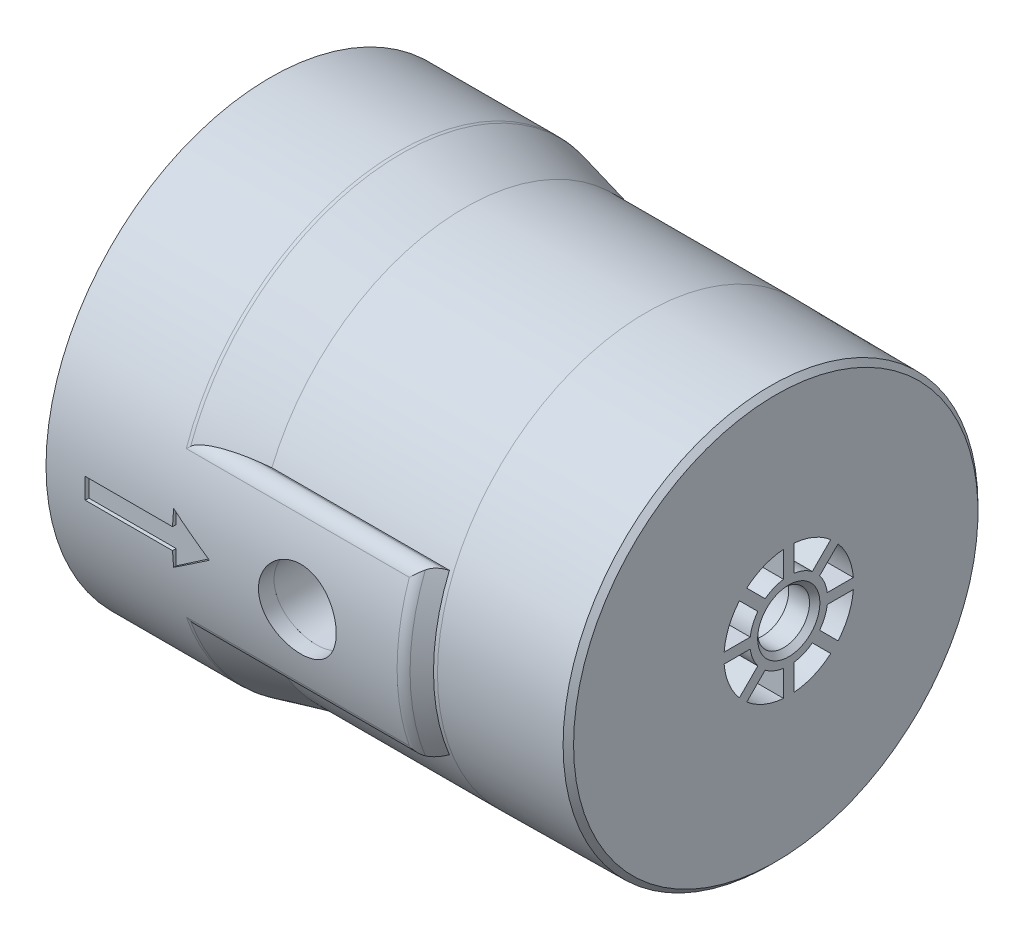
SolidWorks part; units mm, degrees
ref_plane "Front Plane" through (0, 0, 0) normal (0, 0, 1) x (1, 0, 0)
ref_plane "Top Plane" through (0, 0, 0) normal (0, 1, 0) x (1, 0, 0)
ref_plane "Right Plane" through (0, 0, 0) normal (1, 0, 0) x (0, 0, -1)
sketch "Sketch1" plane through (0, 0, 0) normal (0, 0, 1) x (1, 0, 0)
  line L0 (-80.1124, 0) -> (69.6237, 0) construction
  line L1 (-80.2087, 17.3) -> (-70.2087, 17.3)
  line L2 (-70.2087, 17.3) -> (-65.2087, 16.1)
  line L3 (-65.2087, 16.1) -> (-51.2087, 16.1)
  line L4 (-80.2087, 16.1) -> (-70.2092, 16.1)
  line L5 (-70.2092, 16.1) -> (-65.2092, 14.9)
  line L6 (-65.2092, 14.9) -> (-45.2092, 14.9)
  line L7 (-80.2087, 17.3) -> (-80.2087, 16.1)
  line L8 (-45.2092, 14.9) -> (-45.2092, 0)
  line L9 (-45.2092, 0) -> (-41.2092, 0)
  line L10 (-41.2092, 0) -> (-41.2092, 16)
  line L11 (-41.2092, 16) -> (-51.2087, 16.1)
  line L12 (-70.2087, 17.3) -> (-70.2092, 16.1) construction
  dimension "D2" = 10
  dimension "D3" = 16.1
  dimension "D4" = 10
  dimension "D5" = 14
  dimension "D6" = 5
  dimension "D7" = 16.1
  dimension "D8" = 41.2092
  dimension "D9" = 20
  dimension "D1" = 4
  dimension "D10" = 5
  dimension "D11" = 16
  dimension "D12" = 1.2
  dimension "D13" = 1.2
revolve "Revolve1" add sketch "Sketch1" angle 360 about L0
sketch "Sketch2" plane through (-41.2092, 0, 0) normal (1, 0, 0) x (0, 0, -1)
  line L0 (1, 0) -> (-21.0341, 0) construction
  line L1 (-3.984, 0.4) -> (-3.482, 0.4)
  line L3 (1, 0) -> (-21.0341, 0) construction
  line L10 (1, 0) -> (-16.203, 17.203) construction
  line L11 (-1.3852, 1.8195) -> (-1.9187, 2.353)
  line L12 (-3.482, 0.4) -> (-1.9732, 0.4)
  line L13 (-1.9187, 2.353) -> (-2.807, 3.2414)
  line L14 (0.6, 3.7276) -> (0.6, 4.984)
  line L15 (-2.2414, 3.807) -> (-1.8864, 3.4521)
  line L16 (0.6, 2.9732) -> (0.6, 3.7276)
  line L17 (-1.8864, 3.4521) -> (-0.8195, 2.3852)
  line L18 (3.353, 2.9187) -> (4.2414, 3.807)
  line L19 (1.4, 4.984) -> (1.4, 4.482)
  line L20 (2.8195, 2.3852) -> (3.353, 2.9187)
  line L21 (1.4, 4.482) -> (1.4, 2.9732)
  line L22 (4.7276, 0.4) -> (5.984, 0.4)
  line L23 (4.807, 3.2414) -> (4.4521, 2.8864)
  line L24 (3.9732, 0.4) -> (4.7276, 0.4)
  line L25 (4.4521, 2.8864) -> (3.3852, 1.8195)
  line L26 (3.9187, -2.353) -> (4.807, -3.2414)
  line L27 (5.984, -0.4) -> (5.482, -0.4)
  line L28 (3.3852, -1.8195) -> (3.9187, -2.353)
  line L29 (5.482, -0.4) -> (3.9732, -0.4)
  line L30 (1.4, -3.7276) -> (1.4, -4.984)
  line L31 (4.2414, -3.807) -> (3.8864, -3.4521)
  line L32 (1.4, -2.9732) -> (1.4, -3.7276)
  line L33 (3.8864, -3.4521) -> (2.8195, -2.3852)
  line L34 (-1.353, -2.9187) -> (-2.2414, -3.807)
  line L35 (0.6, -4.984) -> (0.6, -4.482)
  line L36 (-0.8195, -2.3852) -> (-1.353, -2.9187)
  line L37 (0.6, -4.482) -> (0.6, -2.9732)
  line L38 (-2.7276, -0.4) -> (-3.984, -0.4)
  line L39 (-2.807, -3.2414) -> (-2.4521, -2.8864)
  line L40 (-1.9732, -0.4) -> (-2.7276, -0.4)
  line L41 (-2.4521, -2.8864) -> (-1.3852, -1.8195)
  circle A9 centre (0, 0) radius 16 construction
  arc A11 (-1.9732, 0.4) -> (-1.3852, 1.8195) centre (1, 0) cw
  arc A15 (-3.984, 0.4) -> (-2.807, 3.2414) centre (1, 0) cw
  arc A18 (-2.2414, 3.807) -> (0.6, 4.984) centre (1, 0) cw
  arc A21 (-0.8195, 2.3852) -> (0.6, 2.9732) centre (1, 0) cw
  arc A22 (1.4, 4.984) -> (4.2414, 3.807) centre (1, 0) cw
  arc A25 (1.4, 2.9732) -> (2.8195, 2.3852) centre (1, 0) cw
  arc A26 (4.807, 3.2414) -> (5.984, 0.4) centre (1, 0) cw
  arc A29 (3.3852, 1.8195) -> (3.9732, 0.4) centre (1, 0) cw
  arc A30 (5.984, -0.4) -> (4.807, -3.2414) centre (1, 0) cw
  arc A33 (3.9732, -0.4) -> (3.3852, -1.8195) centre (1, 0) cw
  arc A34 (4.2414, -3.807) -> (1.4, -4.984) centre (1, 0) cw
  arc A37 (2.8195, -2.3852) -> (1.4, -2.9732) centre (1, 0) cw
  arc A38 (0.6, -4.984) -> (-2.2414, -3.807) centre (1, 0) cw
  arc A41 (0.6, -2.9732) -> (-0.8195, -2.3852) centre (1, 0) cw
  arc A42 (-2.807, -3.2414) -> (-3.984, -0.4) centre (1, 0) cw
  arc A45 (-1.3852, -1.8195) -> (-1.9732, -0.4) centre (1, 0) cw
  point P11 (1, 0)
  point P27 (2, 0)
  point P74 (1, 0)
  dimension "D2" = 0.4
  dimension "D4" = 3
  dimension "D8" = 5
  dimension "D9" = 8
  dimension "D1" = 45
  dimension "D3" = 0.4
  dimension "D5" = 1
ref_plane "Plane1" through (0, 0, 12) normal (0, 0, 1) x (1, 0, 0)
extrude "Cut-Extrude5" cut sketch "Sketch2" against normal up to next
ref_plane "Plane3" through (0, 0, -1) normal (0, 0, -1) x (-1, 0, 0)
sketch "Sketch8" plane through (0, 0, -1) normal (0, 0, -1) x (-1, 0, 0)
  line L0 (41.4715, 0) -> (64.2594, 0) construction
  line L1 (45.2092, -2.5) -> (43.2092, -2.5)
  line L2 (41.2092, 16) -> (41.2092, -16) construction
  line L3 (45.2092, -2.5) -> (45.2092, 0)
  line L4 (41.2092, -2) -> (41.2092, 0)
  line L5 (45.2092, 0) -> (41.2092, 0)
  line L6 (43.2092, -2.5) -> (43.2092, -2)
  line L7 (43.2092, -2) -> (41.2092, -2)
  dimension "D1" = 2.5
  dimension "D2" = 2
  dimension "D3" = 4
  dimension "D4" = 2
revolve "Cut-Revolve2" cut sketch "Sketch8" angle 360 about L0
chamfer "Chamfer1" distance 0.4 angle 45 3 edges at (-41.2092, 0, 16) (-80.2087, 0, 16.1) (-41.2092, 0, -3) first distance on face at (-41.2092, 0, -3) first distance on face at (-80.2087, 0, 16.1)
fillet "Fillet4" radius 10 1 edges at (-70.2092, 0, 16.1)
sketch "Sketch12" plane through (0, 0, 0) normal (0, 1, 0) x (1, 0, 0)
  line L0 (-38.7859, 0) -> (-87.7556, 0) construction
  line L1 (-51.5117, -16.103) -> (-65.2087, -16.1)
  line L3 (-70.2087, -17.3) -> (-52.7087, -17.3)
  line L4 (-70.2092, 17.2) -> (-65.2092, 16)
  line L5 (-65.2087, -16.1) -> (-70.2087, -17.3)
  line L6 (-65.2087, -16.1) -> (-70.2087, -17.3)
  line L7 (-52.7087, -17.3) -> (-51.5117, -16.103)
  line L8 (-65.2092, 16) -> (-41.2092, 16)
  line L9 (-41.6132, -16.004) -> (-51.2087, -16.1)
  line L10 (-41.6132, -16.004) -> (-51.2087, -16.1) construction
  dimension "D1" = 17.5
  dimension "D2" = 45
revolve "Revolve2" add sketch "Sketch12" angle 45 mid plane about L0 region at (-59.976, 0, 16.7251)
ref_plane "Plane4" through (0, 0, 17) normal (0, 0, 1) x (1, 0, 0)
sketch "Sketch13" plane through (0, 0, 17) normal (0, 0, 1) x (1, 0, 0)
  line L0 (-77.1995, 0.799) -> (-70.4645, 0.799)
  line L1 (-70.4645, 1.958) -> (-70.4645, 0.799)
  line L2 (-70.4645, 1.958) -> (-67.6061, 0)
  line L3 (-77.1995, 0.799) -> (-77.1995, -0.799)
  line L4 (-66.0568, 0) -> (-78.8911, 0) construction
  line L5 (-77.1995, -0.799) -> (-70.4645, -0.799)
  line L6 (-70.4645, -1.958) -> (-70.4645, -0.799)
  line L7 (-70.4645, -1.958) -> (-67.6061, 0)
  point P10 (-77.1995, 0)
extrude "Cut-Extrude6" cut sketch "Sketch13" along normal blind 1.2
fillet "Fillet7" radius 1 4 edges at (-61.4587, 6.6204, 15.9831) (-52.7087, 0, 17.3) (-61.4587, -6.6204, 15.9831) (-70.2087, 0, -17.3)
sketch "Sketch3" plane through (0, 0, 12) normal (0, 0, 1) x (1, 0, 0)
  line L6 (-65.8174, 16.2461) -> (-65.8174, -16.2461) construction
  line L7 (-65.8174, 10.2323) -> (-41.2092, 10.2323)
  line L8 (-65.8174, 10.2323) -> (-65.8174, -10.138)
  line L9 (-65.8174, -10.138) -> (-41.2092, -10.138)
  line L10 (-41.2092, 10.2323) -> (-41.2092, -10.138)
  line L11 (-41.2092, -16) -> (-41.2092, 16) construction
extrude "Boss-Extrude1" add sketch "Sketch3" along normal up to body separate body
sketch "Sketch4" plane through (0, 0, 12) normal (0, 0, 1) x (1, 0, 0)
  line L0 (-65.8174, 16.2461) -> (-65.8174, -16.2461) construction
  line L2 (-71.1934, 0) -> (-58.0618, 0) construction
  circle A0 centre (-60.8174, 0) radius 2
  dimension "D2" = 4
  dimension "D1" = 5
extrude "Cut-Extrude2" cut sketch "Sketch4" along normal up to next
ref_plane "Plane2" through (0, 0, 12.8) normal (0, 0, 1) x (1, 0, 0)
sketch "Sketch5" plane through (0, 0, 12.8) normal (0, 0, 1) x (1, 0, 0)
  circle A0 centre (-60.8174, 0) radius 3
  dimension "D1" = 6
extrude "Cut-Extrude4" cut sketch "Sketch5" along normal through all
fillet "Fillet2" radius 2 2 edges at (-55.2092, 8.8323, 12) (-55.2092, -8.8323, 12)
fillet "Fillet9" radius 1 1 edges at (-65.8174, 0, 12)
fillet "Fillet12" radius 0.4 4 edges at (-45.2092, 8.8198, 11.8842) (-45.2092, 0, 12) (-45.2092, -8.8198, 11.8842) (-45.2092, 0, -14.9)
